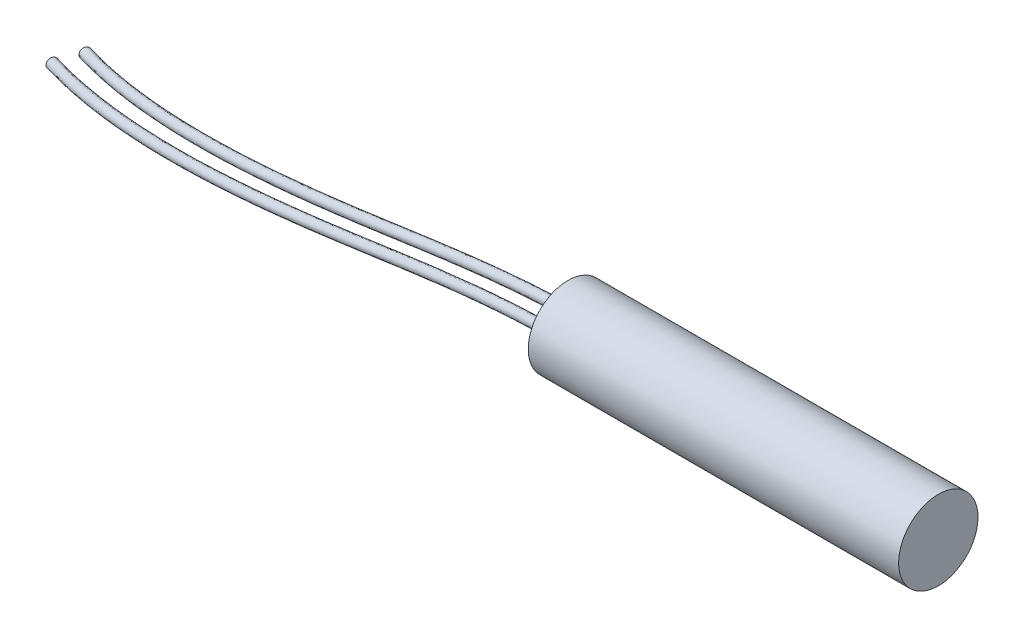
SolidWorks part; units mm, degrees
ref_plane "Front" through (0, 0, 0) normal (0, 0, 1) x (1, 0, 0)
ref_plane "Top" through (0, 0, 0) normal (0, 1, 0) x (1, 0, 0)
ref_plane "Right" through (0, 0, 0) normal (1, 0, 0) x (0, 0, -1)
sketch "Sketch1" plane through (0, 0, 0) normal (1, 0, 0) x (0, 0, -1)
  circle A0 centre (0, 0) radius 3
  dimension "D1" = 6
extrude "Boss-Extrude1" add sketch "Sketch1" along normal blind 28
sketch "Sketch2" plane through (0, 0, 0) normal (0, 1, 0) x (1, 0, 0)
  line L0 (0, 0) -> (-8.4805, 0) construction
  spline S0 degree 3 poles (0, 0) (-5.8116, 0) (-16.7933, -2.4118) (-29.753, -3.2995) (-36.4364, -1.3057) knots 0 0 0 0 0.427107 1 1 1 1
  point P2 (-15.2564, 0)
  point P6 (-24.3378, -2.6404)
  point P7 (-15.7661, 0)
  point P9 (-16.727, 0)
  point P10 (-15.5531, -1.7822)
  point P11 (-36.4364, -1.3057)
sketch "Sketch3" plane through (0, 0, 0) normal (-1, 0, 0) x (0, 0, 1)
  line L0 (0, 0) -> (-1, 0) construction
  line L1 (0, 0) -> (0, 1.1308) construction
  circle A0 centre (-1, 0) radius 0.375
  circle A2 centre (1, 0) radius 0.375
  dimension "D1" = 1
  dimension "D2" = 0.75
sweep "Sweep1" add profiles "Sketch3" path "Sketch2"
